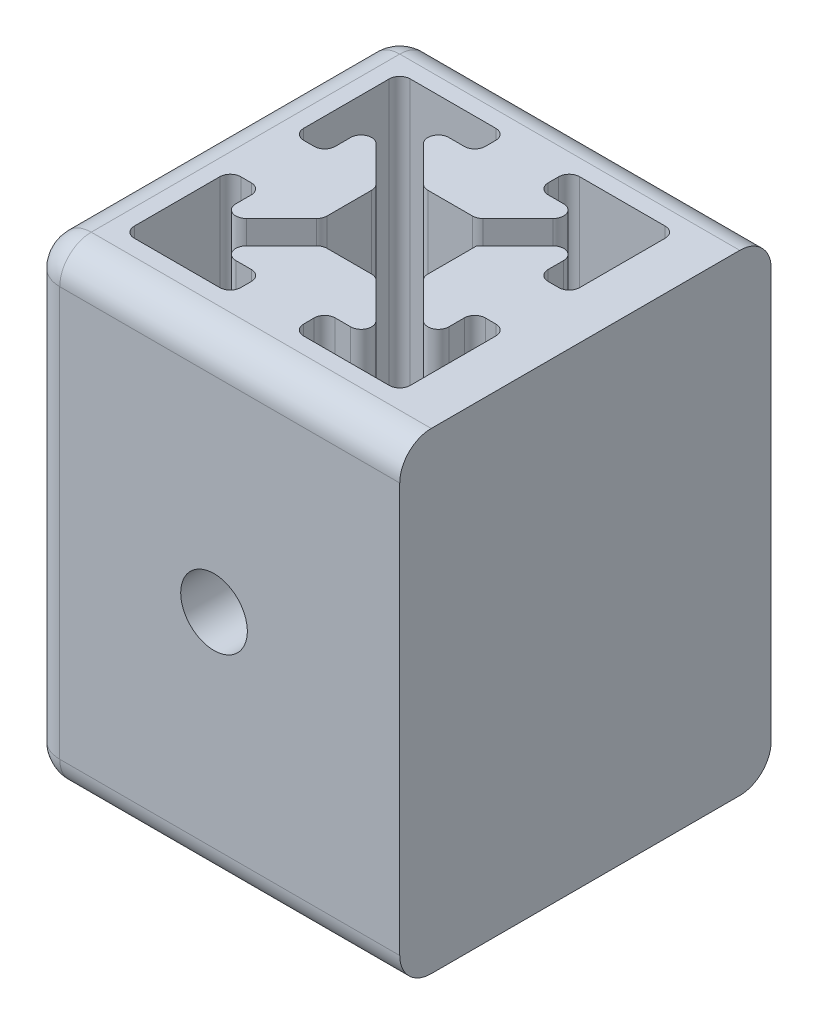
SolidWorks part; units mm, degrees
ref_plane "Front" through (0, 0, 0) normal (0, 0, 1) x (1, 0, 0)
ref_plane "Top" through (0, 0, 0) normal (0, 1, 0) x (1, 0, 0)
ref_plane "Right" through (0, 0, 0) normal (1, 0, 0) x (0, 0, -1)
sketch "Sketch1" plane through (0, 0, 0) normal (0, 1, 0) x (1, 0, 0)
  line L1 (-17.7, -17.7) -> (17.7, -17.7)
  line L2 (-17.7, -17.7) -> (-17.7, 17.7)
  line L3 (-17.7, 17.7) -> (17.7, 17.7)
  line L4 (17.7, -17.7) -> (17.7, 17.7)
  line L5 (-17.7, -17.7) -> (17.7, 17.7) construction
  line L6 (-17.7, 17.7) -> (17.7, -17.7) construction
  point P0 (0, 0)
  dimension "D1" = 35.4
extrude "Boss-Extrude1" add sketch "Sketch1" along normal up to surface (45 mm away)
sketch "Sketch2" plane through (0, 45, 0) normal (0, 1, 0) x (1, 0, 0)
  line L0 (-13.15, -13.15) -> (13.15, -13.15) construction
  line L1 (13.15, -13.15) -> (13.15, 13.15) construction
  line L2 (13.15, 13.15) -> (-13.15, 13.15) construction
  line L3 (-13.15, 13.15) -> (-13.15, -13.15) construction
  line L4 (-13.15, -13.15) -> (13.15, 13.15) construction
  line L5 (-13.15, 13.15) -> (13.15, -13.15) construction
  line L6 (-4.8, 2.5373) -> (-10.15, 7.8873)
  line L7 (-2.5373, 4.8) -> (2.5373, 4.8)
  line L8 (-4.8, 2.5373) -> (-4.8, -2.5373)
  line L9 (-2.5373, -4.8) -> (2.5373, -4.8)
  line L10 (4.8, 2.5373) -> (4.8, -2.5373)
  line L11 (-4.8, 4.8) -> (4.4727, -4.4727) construction
  line L12 (-4.8, -4.8) -> (3.8995, 3.8995) construction
  line L13 (-10.15, 7.8873) -> (-10.15, 3)
  line L14 (-10.15, 3) -> (-13.15, 3)
  line L15 (-13.15, 3) -> (-13.15, 13.15)
  line L16 (-13.15, 13.15) -> (-3, 13.15)
  line L17 (-3, 13.15) -> (-3, 10.15)
  line L18 (-3, 10.15) -> (-7.8873, 10.15)
  line L19 (-7.8873, 10.15) -> (-2.5373, 4.8)
  line L20 (-10.15, 7.8873) -> (-7.8873, 10.15) construction
  line L21 (-4.8, 2.5373) -> (-2.5373, 4.8) construction
  line L22 (3, 13.15) -> (13.15, 13.15)
  line L23 (13.15, 13.15) -> (13.15, 3)
  line L24 (13.15, 3) -> (10.15, 3)
  line L25 (10.15, 7.8873) -> (4.8, 2.5373)
  line L26 (10.15, 3) -> (10.15, 7.8873)
  line L27 (2.5373, 4.8) -> (7.8873, 10.15)
  line L28 (7.8873, 10.15) -> (3, 10.15)
  line L29 (3, 10.15) -> (3, 13.15)
  line L30 (13.15, -3) -> (13.15, -13.15)
  line L31 (13.15, -13.15) -> (3, -13.15)
  line L32 (3, -13.15) -> (3, -10.15)
  line L33 (7.8873, -10.15) -> (2.5373, -4.8)
  line L34 (3, -10.15) -> (7.8873, -10.15)
  line L35 (4.8, -2.5373) -> (10.15, -7.8873)
  line L36 (10.15, -7.8873) -> (10.15, -3)
  line L37 (10.15, -3) -> (13.15, -3)
  line L38 (-3, -13.15) -> (-13.15, -13.15)
  line L39 (-13.15, -13.15) -> (-13.15, -3)
  line L40 (-13.15, -3) -> (-10.15, -3)
  line L41 (-10.15, -7.8873) -> (-4.8, -2.5373)
  line L42 (-10.15, -3) -> (-10.15, -7.8873)
  line L43 (-2.5373, -4.8) -> (-7.8873, -10.15)
  line L44 (-7.8873, -10.15) -> (-3, -10.15)
  line L45 (-3, -10.15) -> (-3, -13.15)
  point P2 (0, 0)
  point P5 (0, 0)
  point P18 (0, 13.15)
  point P50 (0, 0)
  dimension "D1" = 26.3
  dimension "D2" = 9.6
  dimension "D3" = 3
  dimension "D4" = 3.2
  dimension "D5" = 3
  dimension "D6" = 4
extrude "Cut-Extrude1" cut sketch "Sketch2" against normal up to surface (45 mm away) up to face at (0, 0, 0)
fillet "Fillet1" radius 1 35 edges at (-3, 22.5, -13.15) (-3, 22.5, -10.15) (-7.8873, 22.5, -10.15) (-2.5373, 22.5, -4.8) (-13.15, 22.5, -13.15) (-13.15, 22.5, -3) (-10.15, 22.5, -7.8873) (-10.15, 22.5, -3) (-4.8, 22.5, -2.5373) (-13.15, 22.5, 3) (-10.15, 22.5, 3) (-10.15, 22.5, 7.8873) (-13.15, 22.5, 13.15) (-3, 22.5, 13.15) (-7.8873, 22.5, 10.15) (-4.8, 22.5, 2.5373) (-2.5373, 22.5, 4.8) (2.5373, 22.5, 4.8) (4.8, 22.5, 2.5373) (7.8873, 22.5, 10.15) (10.15, 22.5, 7.8873) (-3, 22.5, 10.15) (3, 22.5, 10.15) (3, 22.5, 13.15) (13.15, 22.5, 13.15) (13.15, 22.5, 3) (10.15, 22.5, 3) (10.15, 22.5, -3) (13.15, 22.5, -3) (13.15, 22.5, -13.15) (3, 22.5, -13.15) (3, 22.5, -10.15) (7.8873, 22.5, -10.15) (2.5373, 22.5, -4.8) (10.15, 22.5, -7.8873)
ref_axis "Axis1" through (0, 50, 0) along (0, -1, 0)
sketch "Sketch3" plane through (0, 0, -17.7) normal (0, 0, -1) x (-1, 0, 0)
  line L0 (-17.7, 22.5) -> (0, 22.5) construction
  line L1 (-17.7, 45) -> (-17.7, 0) construction
  line L2 (0, 22.5) -> (17.7, 22.5) construction
  line L3 (17.7, 45) -> (17.7, 0) construction
  line L4 (0, 45) -> (0, 22.5) construction
  line L6 (17.7, 45) -> (-17.7, 45) construction
  line L7 (0, 22.5) -> (0, 0) construction
  circle A0 centre (0, 22.5) radius 3.175
  dimension "D1" = 6.35
extrude "Cut-Extrude2" cut sketch "Sketch3" against normal up to surface (35.4 mm away) contours A0 up to face at (0, 22.5, 17.7)
sketch "Sketch4" plane through (-17.7, 0, 0) normal (-1, 0, 0) x (0, 0, 1)
  line L0 (-17.7, 22.5) -> (0, 22.5) construction
  line L1 (-17.7, 45) -> (-17.7, 0) construction
  line L2 (0, 22.5) -> (17.7, 22.5) construction
  line L3 (17.7, 45) -> (17.7, 0) construction
  line L4 (0, 45) -> (0, 22.5) construction
  line L5 (17.7, 45) -> (-17.7, 45) construction
  line L6 (0, 22.5) -> (0, 0) construction
  line L7 (-17.7, 0) -> (17.7, 0) construction
  circle A0 centre (0, 22.5) radius 3.175
  dimension "D1" = 6.35
extrude "Cut-Extrude3" cut sketch "Sketch4" against normal up to surface (12.9 mm away) up to face at (-4.8, 22.5, 0)
fillet "Fillet2" radius 3 8 edges at (0, 0, 17.7) (0, 0, -17.7) (-17.7, 0, 0) (0, 45, -17.7) (-17.7, 45, 0) (0, 45, 17.7) (-17.7, 22.5, 17.7) (-17.7, 22.5, -17.7)
